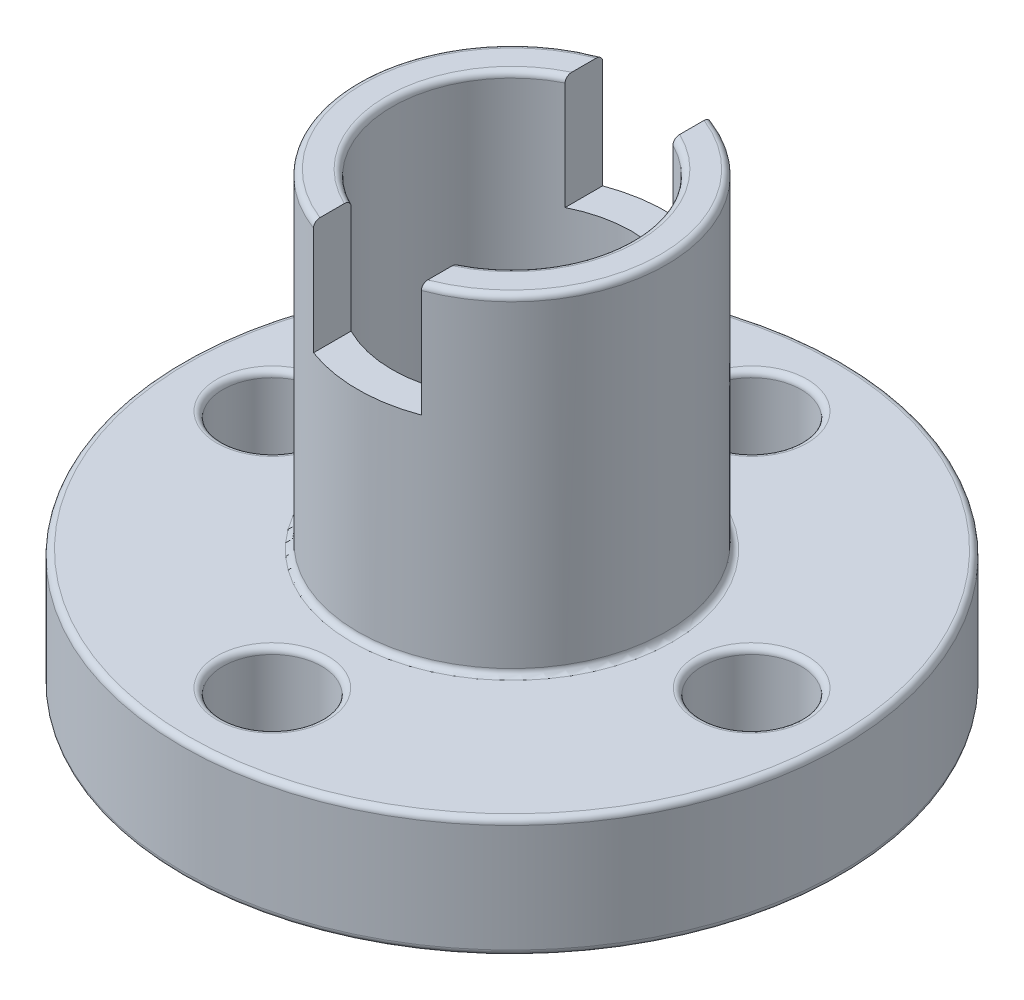
SolidWorks part; units mm, degrees
ref_plane "前视基准面" through (0, 0, 0) normal (0, 0, 1) x (1, 0, 0)
ref_plane "上视基准面" through (0, 0, 0) normal (0, 1, 0) x (1, 0, 0)
ref_plane "右视基准面" through (0, 0, 0) normal (1, 0, 0) x (0, 0, -1)
sketch "草图1" plane through (0, 0, 0) normal (0, 1, 0) x (1, 0, 0)
  circle A0 centre (0, 0) radius 4
  circle A1 centre (0, 0) radius 5.15
  circle A2 centre (0, 0) radius 11
  circle A3 centre (0, 0) radius 8 construction
  circle A4 centre (0, 8) radius 1.65
  circle A5 centre (8, 0) radius 1.65
  circle A6 centre (0, -8) radius 1.65
  circle A7 centre (-8, 0) radius 1.65
  point P8 (0, 0)
  point P9 (-8, 0)
  dimension "D1" = 22
  dimension "D2" = 10.3
  dimension "D3" = 8
  dimension "D4" = 16
  dimension "D5" = 3.3
  dimension "D6" = 4
extrude "凸台-拉伸1" add sketch "草图1" along normal blind 4 contours A2 A7 A6 A5 A4 A1 region at (-10.6889, 0, 0)
extrude "凸台-拉伸2" add sketch "草图1<3>" along normal blind 15 contours A1 A0 region at (-5.0043, 0, 0)
sketch "草图1<3>" plane through (0, 0, 0) normal (0, 1, 0) x (1, 0, 0) same geometry as "草图1"
fillet "圆角1" radius 0.2 14 edges at (0, 15, 5.15) (0, 15, 4) (0, 4, 11) (0, 4, 5.15) (0, 4, -6.35) (8, 4, 1.65) (0, 4, 9.65) (-8, 4, 1.65) (0, 0, 4) (0, 0, 11) (0, 0, -6.35) (8, 0, 1.65) (0, 0, 9.65) (-8, 0, 1.65)
sketch "草图2" plane through (0, 0, 0) normal (0, 0, 1) x (1, 0, 0)
  line L0 (0, 17.5637) -> (0, -3.2504)
  line L1 (-4.95, 15) -> (4.95, 15)
  line L2 (4.95, 15) -> (-4.95, 15) construction
  line L3 (-4.95, 11.2) -> (4.95, 11.2)
  line L4 (-1.8, 17.5637) -> (-1.8, -3.2504)
  line L5 (1.8, 17.5637) -> (1.8, -3.2504)
  arc A1 (-4.95, 15) -> (-5.15, 14.8) centre (-4.95, 14.8) ccw construction
  dimension "D1" = 3.8
  dimension "D2" = 1.8
  dimension "D3" = 1.8
extrude "切除-拉伸1" cut sketch "草图2" against normal through all both and the other way through all contours L1 L4 L3 L0 | L5 L1 L0 L3 region at (0.9, 13.1, 0) region at (-0.9, 13.1, 0)
